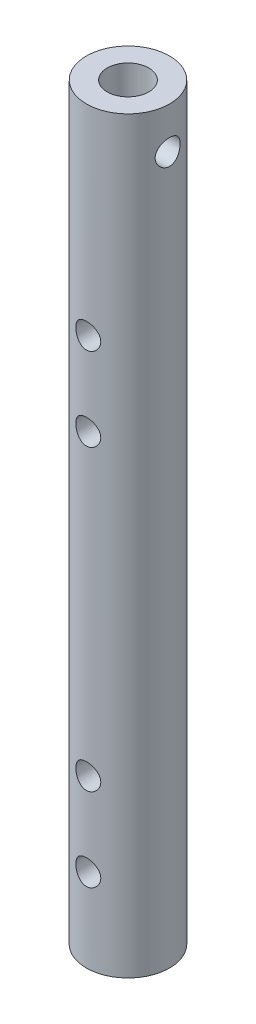
SolidWorks part; units mm, degrees
ref_plane "Front Plane" through (0, 0, 0) normal (0, 0, 1) x (1, 0, 0)
ref_plane "Top Plane" through (0, 0, 0) normal (0, 1, 0) x (1, 0, 0)
ref_plane "Right Plane" through (0, 0, 0) normal (1, 0, 0) x (0, 0, -1)
sketch "Sketch1" plane through (0, 0, 0) normal (0, 1, 0) x (1, 0, 0)
  circle A0 centre (0, 0) radius 2.5
  circle A1 centre (0, 0) radius 5
  dimension "D1" = 10
  dimension "D2" = 5
extrude "Boss-Extrude1" add sketch "Sketch1" along normal blind 90
sketch "Sketch2" plane through (0, 0, 0) normal (0, 0, 1) x (1, 0, 0)
  line L0 (-5, 0) -> (5, 0) construction
  circle A0 centre (0, 65.87) radius 1.5
  circle A1 centre (0, 55.87) radius 1.5
  circle A2 centre (0, 20) radius 1.5
  circle A3 centre (0, 10) radius 1.5
  dimension "D1" = 3
  dimension "D2" = 3
  dimension "D3" = 3
  dimension "D4" = 3
  dimension "D5" = 10
  dimension "D6" = 10
  dimension "D7" = 35.87
  dimension "D8" = 10
extrude "Cut-Extrude1" cut sketch "Sketch2" against normal blind 90 and the other way blind 90
sketch "Sketch3" plane through (0, 0, 0) normal (0, -1, 0) x (1, 0, 0)
  circle A0 centre (0, 0) radius 3
  dimension "D1" = 6
extrude "Cut-Extrude2" cut sketch "Sketch3" against normal blind 7
sketch "Sketch4" plane through (0, 0, 0) normal (1, 0, 0) x (0, 0, -1)
  line L0 (5, 90) -> (-5, 90) construction
  circle A0 centre (0, 85) radius 1.5
  dimension "D1" = 3
  dimension "D2" = 5
extrude "Cut-Extrude3" cut sketch "Sketch4" against normal blind 30 and the other way blind 30
